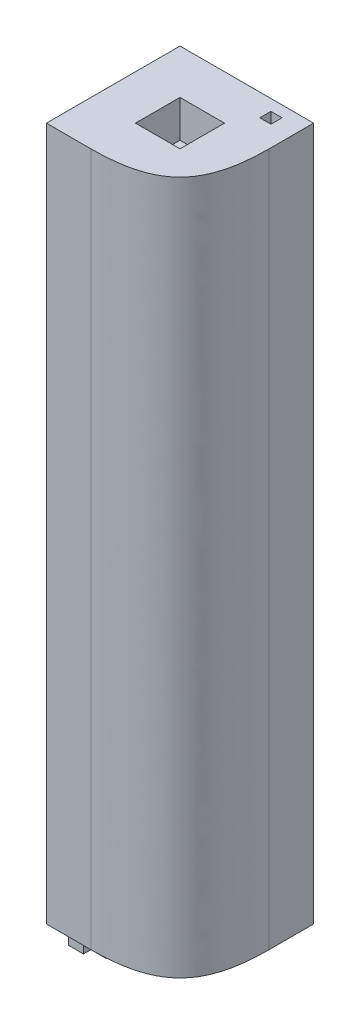
SolidWorks part; units mm, degrees
ref_plane "Front Plane" through (0, 0, 0) normal (0, 0, 1) x (1, 0, 0)
ref_plane "Top Plane" through (0, 0, 0) normal (0, 1, 0) x (1, 0, 0)
ref_plane "Right Plane" through (0, 0, 0) normal (1, 0, 0) x (0, 0, -1)
sketch "Sketch1" plane through (0, 0, 0) normal (0, 1, 0) x (1, 0, 0)
  line L1 (0, 0) -> (36, 0)
  line L2 (0, 0) -> (0, 36)
  line L3 (0, 36) -> (36, 36)
  line L4 (36, 0) -> (36, 36)
  dimension "D1" = 36
  dimension "D2" = 36
extrude "Boss-Extrude1" add sketch "Sketch1" along normal blind 186.9
fillet "Fillet1" radius 24 1 edges at (36, 93.45, 0) conic rho 0.55
sketch "Sketch2" plane through (0, 0, 0) normal (0, -1, 0) x (1, 0, 0)
  line L0 (36, -24) -> (36, -36) construction
  line L1 (0, -12.5) -> (14.28, -12.5)
  line L2 (0, -12.5) -> (0, -36)
  line L3 (0, -36) -> (14.28, -36)
  line L4 (14.28, -12.5) -> (14.28, -36)
  line L5 (0, 0) -> (12, 0) construction
  line L6 (0, -36) -> (0, 0) construction
  line L7 (36, -36) -> (0, -36) construction
  dimension "D1" = 21.72
  dimension "D2" = 12.5
  dimension "D3" = 0
  dimension "D4" = 0
extrude "Cut-Extrude1" cut sketch "Sketch2" against normal blind 27
sketch "Sketch3" plane through (0, 27, 0) normal (0, -1, 0) x (1, 0, 0)
  line L0 (0, -12.5) -> (0, -36) construction
  line L1 (0, -15) -> (11.78, -15)
  line L2 (0, -15) -> (0, -36)
  line L3 (0, -36) -> (11.78, -36)
  line L4 (11.78, -15) -> (11.78, -36)
  line L5 (0, -36) -> (14.28, -36) construction
  line L6 (14.28, -12.5) -> (0, -12.5) construction
  line L7 (14.28, -36) -> (14.28, -12.5) construction
  dimension "D1" = 2.5
  dimension "D2" = 2.5
extrude "Cut-Extrude2" cut sketch "Sketch3" against normal blind 8
sketch "Sketch4" plane through (0, 0, 0) normal (0, -1, 0) x (1, 0, 0)
  line L0 (36, -24) -> (36, -36) construction
  line L1 (0, 0) -> (12, 0) construction
  circle A0 centre (21, -15) radius 2
  dimension "D1" = 4
  dimension "D2" = 15
  dimension "D3" = 15
extrude "Cut-Extrude3" cut sketch "Sketch4" against normal blind 5
sketch "Sketch5" plane through (0, 0, 0) normal (0, -1, 0) x (1, 0, 0)
  line L0 (36, -24) -> (36, -36) construction
  line L1 (18.28, -28) -> (22.28, -28)
  line L2 (18.28, -28) -> (18.28, -32)
  line L3 (18.28, -32) -> (32, -32)
  line L4 (32, -28) -> (32, -32)
  line L5 (36, -36) -> (14.28, -36) construction
  line L6 (14.28, -36) -> (14.28, -12.5) construction
  line L7 (0, 0) -> (12, 0) construction
  line L8 (4, -2) -> (8, -2)
  line L9 (4, -2) -> (4, -10.5)
  line L10 (4, -10.5) -> (8, -10.5)
  line L11 (8, -2) -> (8, -4)
  line L12 (14.28, -12.5) -> (0, -12.5) construction
  line L13 (0, -12.5) -> (0, 0) construction
  line L14 (8, -8.5) -> (8, -10.5)
  line L15 (8, -4) -> (12, -4)
  line L17 (8, -8.5) -> (12, -8.5)
  line L18 (12, -4) -> (12, -8.5)
  line L20 (22.28, -28) -> (22.28, -24)
  line L21 (22.28, -24) -> (28, -24)
  line L22 (28, -28) -> (28, -24)
  line L23 (28, -28) -> (32, -28)
  dimension "D1" = 4
  dimension "D2" = 4
  dimension "D3" = 4
  dimension "D4" = 4
  dimension "D5" = 2
  dimension "D6" = 2
  dimension "D7" = 4
  dimension "D8" = 4
  dimension "D9" = 2
  dimension "D10" = 2
  dimension "D11" = 4
  dimension "D12" = 4
  dimension "D13" = 4
  dimension "D14" = 4
  dimension "D15" = 24
  dimension "D16" = 24
extrude "Boss-Extrude2" add sketch "Sketch5" along normal blind 4
sketch "Sketch6" plane through (0, 0, -36) normal (0, 0, -1) x (-1, 0, 0)
  line L0 (-36, 186.9) -> (0, 186.9) construction
  line L1 (-32, 182.9) -> (-26, 182.9)
  line L2 (-32, 182.9) -> (-32, 178.9)
  line L3 (-32, 178.9) -> (-26, 178.9)
  line L4 (-26, 182.9) -> (-26, 178.9)
  line L5 (-36, 186.9) -> (-36, 0) construction
  line L6 (0, 186.9) -> (0, 35) construction
  line L7 (-10, 182.9) -> (-4, 182.9)
  line L8 (-10, 182.9) -> (-10, 178.9)
  line L9 (-10, 178.9) -> (-4, 178.9)
  line L10 (-4, 182.9) -> (-4, 178.9)
  line L12 (-32, 162.9) -> (-26, 162.9)
  line L13 (-32, 162.9) -> (-32, 158.9)
  line L14 (-32, 158.9) -> (-26, 158.9)
  line L15 (-26, 162.9) -> (-26, 158.9)
  dimension "D1" = 4
  dimension "D2" = 4
  dimension "D3" = 6
  dimension "D4" = 4
  dimension "D5" = 6
  dimension "D6" = 4
  dimension "D7" = 4
  dimension "D8" = 4
  dimension "D9" = 16
  dimension "D10" = 4
extrude "Cut-Extrude4" cut sketch "Sketch6" against normal blind 9
sketch "Sketch7" plane through (0, 186.9, 0) normal (0, 1, 0) x (1, 0, 0)
  line L0 (36, 36) -> (0, 36) construction
  line L1 (27.5, 33) -> (30.5, 33)
  line L2 (27.5, 33) -> (27.5, 30)
  line L3 (27.5, 30) -> (30.5, 30)
  line L4 (30.5, 33) -> (30.5, 30)
  line L5 (36, 24) -> (36, 36) construction
  line L6 (0, 0) -> (12, 0) construction
  line L7 (12, 24) -> (24, 24)
  line L8 (12, 24) -> (12, 12)
  line L9 (12, 12) -> (24, 12)
  line L10 (24, 24) -> (24, 12)
  dimension "D1" = 3
  dimension "D2" = 3
  dimension "D3" = 3
  dimension "D4" = 5.5
  dimension "D5" = 12
  dimension "D6" = 12
  dimension "D7" = 12
  dimension "D8" = 12
extrude "Cut-Extrude5" cut sketch "Sketch7" against normal blind 10
